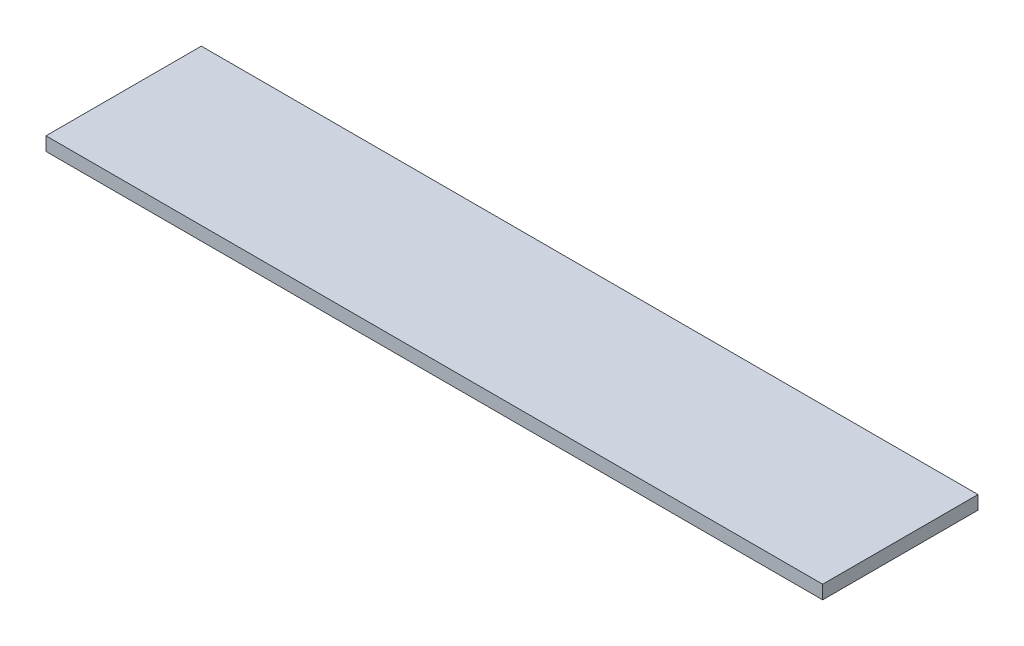
SolidWorks part; units mm, degrees
material "Pino"
ref_plane "Piano frontale" through (0, 0, 0) normal (0, 0, 1) x (1, 0, 0)
ref_plane "Piano superiore" through (0, 0, 0) normal (0, 1, 0) x (1, 0, 0)
ref_plane "Piano destro" through (0, 0, 0) normal (1, 0, 0) x (0, 0, -1)
sketch "Schizzo1" plane through (0, 0, 0) normal (0, 1, 0) x (1, 0, 0)
  line L1 (0, 0) -> (400, 0)
  line L2 (0, 0) -> (0, 80)
  line L3 (0, 80) -> (400, 80)
  line L4 (400, 0) -> (400, 80)
  dimension "D1" = 400
  dimension "D2" = 80
extrude "Estrusione-Estrusione1" add sketch "Schizzo1" along normal blind 7
